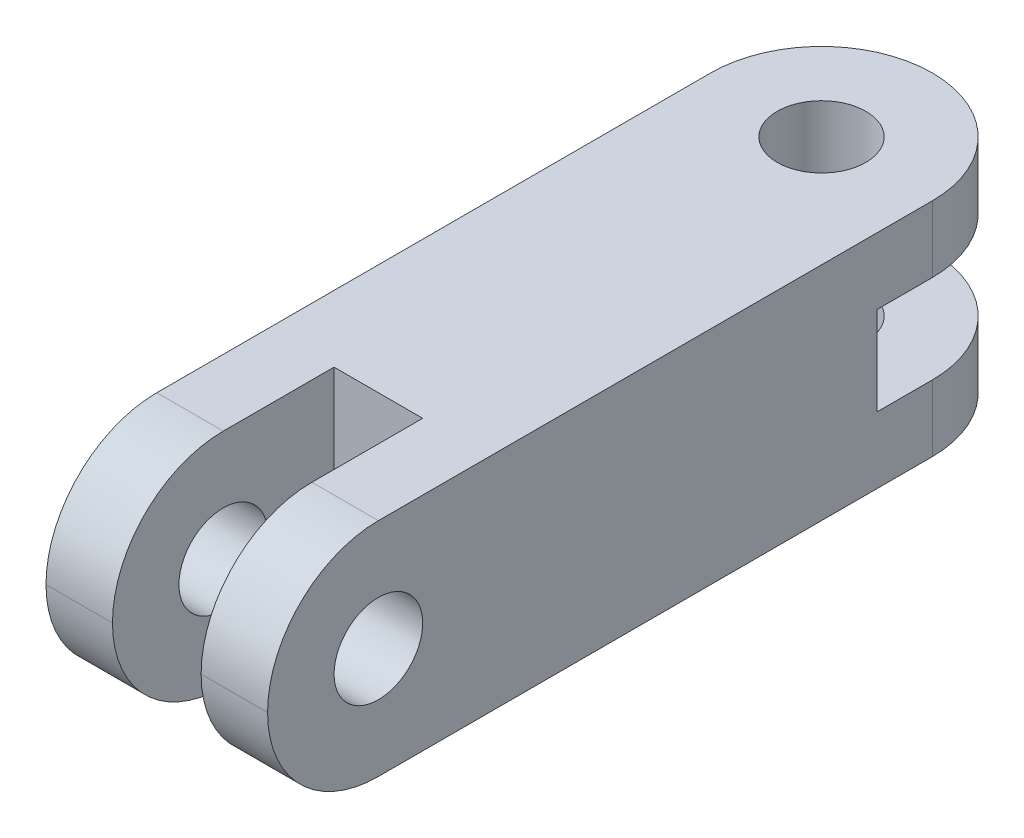
SolidWorks part; units mm, degrees
ref_plane "Front Plane" through (0, 0, 0) normal (0, 0, 1) x (1, 0, 0)
ref_plane "Top Plane" through (0, 0, 0) normal (0, 1, 0) x (1, 0, 0)
ref_plane "Right Plane" through (0, 0, 0) normal (1, 0, 0) x (0, 0, -1)
sketch "Sketch1" plane through (0, 0, 0) normal (1, 0, 0) x (0, 0, -1)
  line L0 (-87.5, 25) -> (-87.5, -25)
  line L1 (-87.5, -25) -> (87.5, -25)
  line L2 (87.5, 25) -> (-87.5, 25)
  line L3 (0, 0) -> (97.028, 0) construction
  line L4 (0, 0) -> (0, 63.6364) construction
  line L5 (87.5, 25) -> (87.5, -25)
  dimension "D1" = 50
  dimension "D2" = 175
  dimension "D3" = 87.5
extrude "Boss-Extrude1" add sketch "Sketch1" along normal blind 25 and the other way blind 25
sketch "Sketch2" plane through (0, 25, 0) normal (0, 1, 0) x (1, 0, 0)
  line L0 (-25, -87.5) -> (25, -87.5) construction
  line L1 (-10, -87.5) -> (10, -87.5)
  line L2 (-10, -87.5) -> (-10, -37.5)
  line L3 (-10, -37.5) -> (10, -37.5)
  line L4 (10, -87.5) -> (10, -37.5)
  line L5 (0, -87.5) -> (0, 41.0378) construction
  line L6 (-25, 87.5) -> (25, 87.5) construction
  dimension "D1" = 20
  dimension "D2" = 50
extrude "Cut-Extrude1" cut sketch "Sketch2" against normal through all
fillet "Fillet2" radius 25 4 edges at (-17.5, 25, 87.5) (17.5, 25, 87.5) (-17.5, -25, 87.5) (17.5, -25, 87.5)
sketch "Sketch3" plane through (25, 0, 0) normal (1, 0, 0) x (0, 0, -1)
  line L0 (0, 0) -> (131.1429, 0) construction
  line L1 (50, 10) -> (106.175, 10)
  line L2 (50, 10) -> (50, -10)
  line L3 (50, -10) -> (106.175, -10)
  line L4 (106.175, 10) -> (106.175, -10)
  line L5 (-62.5, 0) -> (75, 0) construction
  line L6 (87.5, 25) -> (-62.5, 25) construction
  line L7 (-62.5, -25) -> (87.5, -25) construction
  dimension "D1" = 20
  dimension "D2" = 50
  dimension "D3" = 50
sketch "Sketch4" plane through (25, 0, 0) normal (1, 0, 0) x (0, 0, -1)
  line L0 (-62.5, 0) -> (75, 0) construction
  dimension "D1" = 75
extrude "Cut-Extrude2" cut sketch "Sketch3" against normal through all
fillet "Fillet6" radius 25 4 edges at (25, 17.5, -87.5) (25, -17.5, -87.5) (-25, -17.5, -87.5) (-25, 17.5, -87.5)
hole_wizard "Hole1" positions "Sketch5" profile "Sketch6" legacy end condition through all
sketch "Sketch5" plane through (0, 25, 0) normal (0, 1, 0) x (1, 0, 0)
  point P0 (0, 62.5)
sketch "Sketch6" plane through (0, 25, -62.5) normal (1, 0, 0) x (0, 0, 1)
  line L0 (0, 0) -> (0, 50)
  line L1 (0, 50) -> (10, 50)
  line L2 (10, 50) -> (10, 0)
  line L3 (10, 0) -> (0, 0)
  line L4 (0, 110) -> (0, -10) construction
  dimension "Diameter" = 20
  dimension "Depth" = 50
hole_wizard "Hole2" positions "Sketch7" profile "Sketch8" legacy end condition through all
sketch "Sketch7" plane through (-25, 0, 0) normal (-1, 0, 0) x (0, 0, 1)
  point P0 (62.5, 0)
sketch "Sketch8" plane through (-25, 0, 62.5) normal (0, 1, 0) x (0, 0, 1)
  line L0 (0, 0) -> (0, 50)
  line L1 (0, 50) -> (10, 50)
  line L2 (10, 50) -> (10, 0)
  line L3 (10, 0) -> (0, 0)
  line L4 (0, 110) -> (0, -10) construction
  dimension "Diameter" = 20
  dimension "Depth" = 50
